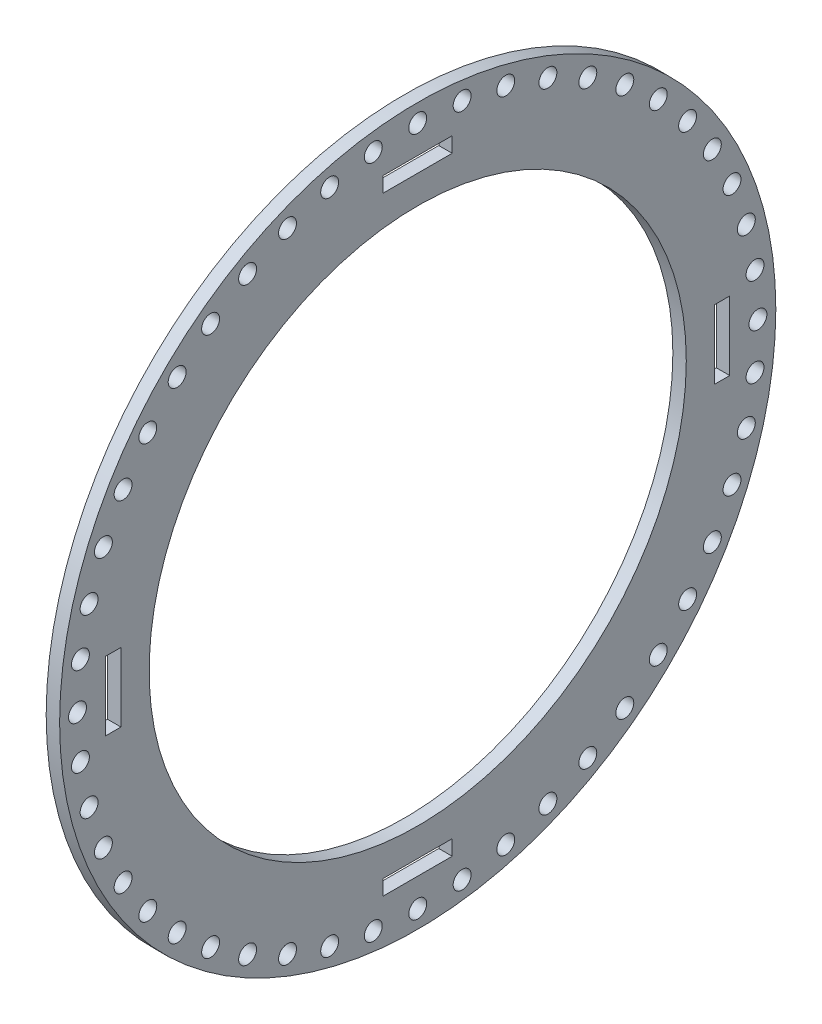
SolidWorks part; units mm, degrees
material "AISI 304"
ref_plane "Front Plane" through (0, 0, 0) normal (0, 0, 1) x (1, 0, 0)
ref_plane "Top Plane" through (0, 0, 0) normal (0, 1, 0) x (1, 0, 0)
ref_plane "Right Plane" through (0, 0, 0) normal (1, 0, 0) x (0, 0, -1)
sketch "Sketch1" plane through (0, 0, 0) normal (1, 0, 0) x (0, 0, -1)
  line L0 (0, 0) -> (0, 40) construction
  line L62 (-3.85, 34.85) -> (3.85, 34.85)
  line L63 (-3.85, 34.85) -> (-3.85, 33.15)
  line L64 (-3.85, 33.15) -> (3.85, 33.15)
  line L65 (3.85, 34.85) -> (3.85, 33.15)
  line L66 (-3.85, 34.85) -> (3.85, 33.15) construction
  line L67 (-3.85, 33.15) -> (3.85, 34.85) construction
  line L103 (34.85, 3.85) -> (34.85, -3.85)
  line L104 (33.15, 3.85) -> (33.15, -3.85)
  line L105 (34.85, 3.85) -> (33.15, 3.85)
  line L106 (34.85, -3.85) -> (33.15, -3.85)
  line L107 (3.85, -34.85) -> (-3.85, -34.85)
  line L108 (3.85, -33.15) -> (-3.85, -33.15)
  line L109 (3.85, -34.85) -> (3.85, -33.15)
  line L110 (-3.85, -34.85) -> (-3.85, -33.15)
  line L111 (-34.85, -3.85) -> (-34.85, 3.85)
  line L112 (-33.15, -3.85) -> (-33.15, 3.85)
  line L113 (-34.85, -3.85) -> (-33.15, -3.85)
  line L114 (-34.85, 3.85) -> (-33.15, 3.85)
  circle A3 centre (0, 0) radius 40
  circle A25 centre (0, 0) radius 30
  point P9 (0, -20)
  point P11 (-20, 0)
  point P22 (0, 34)
  point P29 (20, 0)
  point P31 (0, 30)
  point P75 (0, 0)
  point P81 (0, -1)
  point P93 (0, 0)
  point P95 (0, 0)
  dimension "D2" = 80
  dimension "D3" = 60
  dimension "D7" = 7.7
  dimension "D8" = 1.7
  dimension "D9" = 10
  dimension "D12" = 6
  dimension "D14" = 4
extrude "Boss-Extrude4" add sketch "Sketch1" along normal blind 1.5
sketch "Sketch2" plane through (1.5, 0, 0) normal (1, 0, 0) x (0, 0, -1)
  circle A0 centre (0, 38) radius 1
  circle A1 centre (0, 0) radius 40 construction
  dimension "D2" = 2
  dimension "D1" = 38
extrude "Cut-Extrude2" cut sketch "Sketch2" against normal blind 1.5
pattern_circular "CirPattern3" count 48 over 360 about axis through (1.5, 0, 0) along (1, 0, 0) of "Cut-Extrude2"
